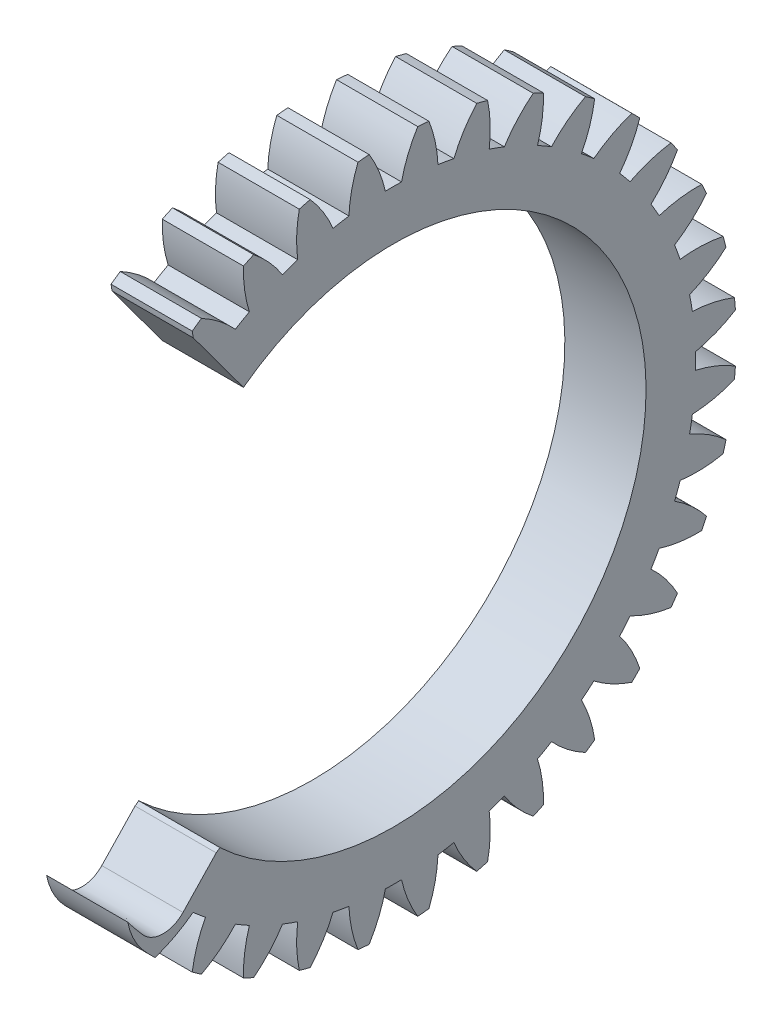
SolidWorks part; units mm, degrees
ref_plane "Plane1" through (0, 0, 0) normal (0, 0, 1) x (1, 0, 0)
ref_plane "Plane2" through (0, 0, 0) normal (0, 1, 0) x (1, 0, 0)
ref_plane "Plane3" through (0, 0, 0) normal (1, 0, 0) x (0, 0, -1)
sketch "HoldingSke" plane through (0, 0, 0) normal (0, 1, 0) x (1, 0, 0)
  line L0 (0, 0) -> (0.4045, -0.2939)
  line L1 (-15, 0) -> (100, 0) construction
  line L2 (0, 0) -> (-2.1039, 2.3779)
  line L3 (0, 0) -> (-11.863, 4.5341)
  line L4 (0, 0) -> (6.9867, 5.0761)
  line L5 (0, 0) -> (-46.8476, -17.4728)
  line L6 (0, 0) -> (-7.4607, -5.0337)
  line L7 (-2.1039, 2.3779) -> (8.6586, 51.2059)
  line L8 (-76.2, 54.61) -> (-71.9, 54.61)
  line L9 (-71.009, 38.7566) -> (-53.1078, 45.2721)
  line L10 (-76.2, 71.12) -> (104.1128, 71.12)
  line L11 (0, 0) -> (-9, 0)
  line L12 (-76.2, 101.6) -> (-76.133, 101.6)
  line L13 (24.9733, 27.94) -> (52.9518, 28.4284)
  line L14 (24.9733, 27.94) -> (24.9743, 27.94)
  line L15 (24.9733, 27.94) -> (100.4006, 29.5858)
  line L16 (-63.627, -2) -> (-12.827, -2)
  circle A0 centre (0, 0) radius 28
  circle A1 centre (0, 0) radius 33.499
  circle A2 centre (0, 0) radius 37.5
  circle A3 centre (0, 0) radius 28
  dimension "Num_teeth" = 36
  dimension "Pitch_radius" = 180.3128
  dimension "Width" = 9
  dimension "Thickness" = 9
sketch "BasProSke" plane through (0, 0, 0) normal (0, 1, 0) x (1, 0, 0)
  line L0 (-10, 0) -> (60, 0) construction
  line L1 (0, 0) -> (0, 38)
  line L2 (0, 0) -> (9, 0)
  line L3 (9, 0) -> (9, 38)
  line L4 (9, 38) -> (0, 38)
  dimension "Thickness" = 9
  dimension "Diameter" = 76
revolve "Base-Revolve" add sketch "BasProSke" angle 360 about L0
sketch "TooCutSke" plane through (0, 0, 0) normal (1, 0, 0) x (0, 0, -1)
  line L1 (0, 0) -> (0, 107) construction
  line L2 (0, 0) -> (-1.6875, 35.9604) construction
  line L3 (0, 0) -> (-6.2701, 71.6676) construction
  line L4 (-1.6875, 35.9604) -> (-3.135, 35.8338) construction
  arc A0 (0.8949, 33.487) -> (-0.8949, 33.487) centre (0, 0) ccw
  arc A1 (2.7061, 37.929) -> (-2.7061, 37.929) centre (0, 0) ccw
  circle A2 centre (0, 0) radius 36 construction
  circle A3 centre (0, 0) radius 33.8289 construction
  arc A4 (-0.8949, 33.487) -> (-2.7061, 37.929) centre (-14.9484, 30.347) ccw
  arc A5 (2.7061, 37.929) -> (0.8949, 33.487) centre (14.9484, 30.347) ccw
extrude "ToothCut" cut sketch "TooCutSke" along normal through all
fillet "Breaks" [suppressed] radius 0.04 tangent propagation no
fillet "RootFillets" [suppressed] radius 0.501
pattern_circular "TeethCuts" count 36 every 10 about axis through (-10, 0, 0) along (1, 0, 0) of "ToothCut", "RootFillets", "Breaks"
sketch "HubNeaOneSke" plane through (0, 0, 0) normal (-1, 0, 0) x (0, 0, 1)
  circle A0 centre (0, 0) radius 33.499
  dimension "Diameter" = 66.998
extrude "HubNearOne" [suppressed] add sketch "HubNeaOneSke" along normal blind 41.0001
sketch "HubNeaBotSke" plane through (0, 0, 0) normal (-1, 0, 0) x (0, 0, 1)
  circle A0 centre (0, 0) radius 33.499
  dimension "Diameter" = 66.998
extrude "HubNearBoth" [suppressed] add sketch "HubNeaBotSke" along normal blind 20.5
ref_plane "FarPln" through (9, 0, 0) normal (1, 0, 0) x (0, 0, -1)
sketch "HubFarSke" plane through (9, 0, 0) normal (1, 0, 0) x (0, 0, -1)
  circle A0 centre (0, 0) radius 33.499
  dimension "Diameter" = 66.998
extrude "HubFar" [suppressed] add sketch "HubFarSke" along normal blind 20.5
sketch "BorSke" plane through (0, 0, 0) normal (1, 0, 0) x (0, 0, -1)
  circle A0 centre (0, 0) radius 28
  dimension "Diameter" = 56
extrude "Bore" cut sketch "BorSke" along normal mid plane 100.0001
sketch "KeySke" plane through (0, 0, 0) normal (1, 0, 0) x (0, 0, -1)
  line L0 (-8, 0) -> (-8, 32.3)
  line L1 (-8, 32.3) -> (8, 32.3)
  line L2 (8, 32.3) -> (8, 0)
  line L3 (0, 0) -> (0, 34) construction
  line L4 (-8, 0) -> (8, 0)
  dimension "Width" = 16
extrude "Keyway" [suppressed] cut sketch "KeySke" along normal mid plane 100.0001
pattern_circular "Keyway2" [suppressed] count 2 every 90 about axis through (-10, 0, 0) along (1, 0, 0) reverse direction yes
sketch "Szkic1" plane through (0, 0, 0) normal (1, 0, 0) x (0, 0, -1)
  line L0 (0, 0) -> (-27.328, 37.0259)
  line L1 (-27.328, 37.0259) -> (-47.6164, -10.233)
  line L2 (-47.6164, -10.233) -> (0, 0)
extrude "Wytnij-wyciągnięcie1" cut sketch "Szkic1" along normal through all
sketch "Szkic2" plane through (0, 0, 0) normal (1, 0, 0) x (0, 0, -1)
  line L0 (-19.6433, -20.6493) -> (-23.3286, -24.5233) construction
  line L1 (-19.6433, -20.6493) -> (-23.3286, -24.5233)
  line L2 (-24.5118, 27.7159) -> (-14.2182, -16.6493)
  line L3 (-14.2182, -16.6493) -> (-19.6433, -20.6493)
  line L4 (-24.5118, 27.7159) -> (-50.9594, 25.255)
  line L5 (-50.9594, 25.255) -> (-37.7356, -29.3697)
  line L6 (-37.7356, -29.3697) -> (-27.7664, -24.4546)
  line L7 (-26.426, -27.3069) -> (-27.3069, -26.426)
  line L8 (-26.426, -27.3069) -> (-25.0675, -25.4318)
  arc A0 (-24.5118, 27.7159) -> (-27.7664, -24.4546) centre (0, 0) ccw construction
  arc A1 (-24.5118, 27.7159) -> (-27.7664, -24.4546) centre (0, 0) ccw
  arc A2 (-27.3069, -26.426) -> (-29.4473, -22.4022) centre (-21.7924, -20.9115) cw
  spline S0 degree 3 poles (101412.4792, 125980.3331) (3768.2153, 5027.8466) (-117.7155, 42.3759) (-27.1426, -24.9996) (-26.9606, -25.1074) (-26.5829, -25.2806) (-26.3868, -25.3469) (-25.9801, -25.4387) (-25.7711, -25.4633) (-25.3572, -25.469) (-25.1483, -25.4503) (-24.7384, -25.37) (-24.5404, -25.3094) (-24.158, -25.1482) (-23.9725, -25.0463) (75.8451, 43.9976) (-4185.8591, 5812.9515) (-98051.1547, 128688.4978) knots -67.877704 -67.877704 -67.877704 -67.877704 0.125 0.125 0.25 0.25 0.375 0.375 0.5 0.5 0.625 0.625 0.75 0.75 0.875 0.875 73.84833 73.84833 73.84833 73.84833 only from (-27.7664, -24.4546) to (-23.3286, -24.5233) construction
  spline S1 degree 3 poles (-27.7664, -24.4546) (-27.6277, -24.6121) (-27.4749, -24.7523) (-27.1426, -24.9996) (-26.9606, -25.1074) (-26.5829, -25.2806) (-26.3868, -25.3469) (-25.9801, -25.4387) (-25.7711, -25.4633) (-25.3572, -25.469) (-25.1483, -25.4503) (-24.7384, -25.37) (-24.5404, -25.3094) (-24.158, -25.1482) (-23.9725, -25.0463) (-23.6312, -24.8102) (-23.4733, -24.6754) (-23.3286, -24.5233) knots 0 0 0 0 0.125 0.125 0.25 0.25 0.375 0.375 0.5 0.5 0.625 0.625 0.75 0.75 0.875 0.875 1 1 1 1
extrude "Wytnij-wyciągnięcie2" cut sketch "Szkic2" against normal blind 43 and the other way through all contours A1 L4 L5 L6 | A1 S1 L1 L3 L2 region at (0, -1.5762, 26.5296) region at (0, 4.8425, 39.1923)
extrude "Dodanie-wyciągnięcie1" add sketch "Szkic2<3>" along normal up to surface (9 mm away) contours A2 L6 A1 | S1 L6 A2 L7 L8 region at (0, -25.7946, 26.8655) region at (0, -23.8723, 28.649) up to face at (9, -1.2954, -9.9994)
sketch "Szkic2<3>" plane through (0, 0, 0) normal (1, 0, 0) x (0, 0, -1) same geometry as "Szkic2"
equation "' \"Module@HoldingSke\" = 6.35"
equation "' \"Num_teeth@HoldingSke\" = 12"
equation "' \"Ap@HoldingSke\" =  20"
equation "' \"Ap@HoldingSke\" = 20"
equation "' \"Width@HoldingSke\" = 0.5 * 25.4"
equation "' \"Hub_dia@HoldingSke\"= 1 * 25.4"
equation "' \"Hub_dia@HoldingSke\" = 1 * 25.4"
equation "' \"Overall_len@HoldingSke\" = 1.0 * 25.4"
equation "' \"Bore@HoldingSke\" = 0.75 * 25.4"
equation "' \"T_dim@HoldingSke\" = 0.1 * 25.4"
equation "' \"Width@KeySke\" = 0.25 * 25.4"
equation "' \"Show_teeth@HoldingSke\" = 13"
equation "' \"Backlash@HoldingSke\" = 0.009 * 25.4"
equation "' \"Addendum_fac@HoldingSke\" = 1.0"
equation "' \"Dedendum_fac@HoldingSke\" = 1.25"
equation "' \"Dedendum_add@HoldingSke\" = 0.00005 * 25.4"
equation "' \"Clearance_fac@HoldingSke\" = 0.25"
equation "\"Pitch@HoldingSke\" = 1 / \"Module@HoldingSke\""
equation "\"Overcut_dia@TooCutSke\" = (\"Num_teeth@HoldingSke\" + 2 * \"Addendum_fac@HoldingSke\") / \"Pitch@HoldingSke\" + 0.002 * 25.4"
equation "\"Pitch_dia@TooCutSke\" = \"Num_teeth@HoldingSke\" / \"Pitch@HoldingSke\""
equation "\"Base_dia@TooCutSke\" = \"Num_teeth@HoldingSke\" / \"Pitch@HoldingSke\" * cos((\"Ap@HoldingSke\"  * 3.14159265 / 180))"
equation "\"Root_dia@TooCutSke\" = (\"Num_teeth@HoldingSke\" + 2) / \"Pitch@HoldingSke\" - 2 * (\"Addendum_fac@HoldingSke\" + \"Dedendum_fac@HoldingSke\") / \"Pitch@HoldingSke\" - \"Dedendum_add@HoldingSke\" * 2"
equation "\"Half_ang@TooCutSke\" = 180 / \"Num_teeth@HoldingSke\""
equation "\"Half_CT@TooCutSke\" = \"Num_teeth@HoldingSke\" / \"Pitch@HoldingSke\" * sin((3.14159265 / 2 / \"Num_teeth@HoldingSke\")) / 2 - 7 * \"Backlash@HoldingSke\" / 4"
equation "\"Flank_rad@TooCutSke\" = \"Num_teeth@HoldingSke\" / \"Pitch@HoldingSke\" / 5"
equation "\"Radius@RootFillets\" = \"Clearance_fac@HoldingSke\" / \"Pitch@HoldingSke\" + \"Dedendum_add@HoldingSke\""
equation "\"Break_rad@Breaks\" = 0.02 / \"Pitch@HoldingSke\""
equation "\"Thickness@HoldingSke\" = \"Width@HoldingSke\""
equation "\"OAL@HoldingSke\" = \"Thickness@HoldingSke\""
equation "\"MHD@HoldingSke\" = (\"Num_teeth@HoldingSke\" + 2) / \"Pitch@HoldingSke\" - 2 * (\"Addendum_fac@HoldingSke\" + \"Dedendum_fac@HoldingSke\")  / \"Pitch@HoldingSke\" - \"Dedendum_add@HoldingSke\" * 2"
equation "\"MBD@HoldingSke\" = (\"Num_teeth@HoldingSke\" + 2) / \"Pitch@HoldingSke\" - 2 * (\"Addendum_fac@HoldingSke\" + \"Dedendum_fac@HoldingSke\")  / \"Pitch@HoldingSke\" - \"Dedendum_add@HoldingSke\" * 2 - 0.002 * 25.4"
equation "\"MHD@HoldingSke\" = ((sgn( \"MHD@HoldingSke\" - \"Hub_dia@HoldingSke\" )-1)*( \"MHD@HoldingSke\" - \"Hub_dia@HoldingSke\" ))/-2+ \"Hub_dia@HoldingSke\""
equation "\"MBD@HoldingSke\" = ((sgn( \"MBD@HoldingSke\" - \"Bore@HoldingSke\" )-1)*( \"MBD@HoldingSke\" - \"Bore@HoldingSke\" ))/-2+ \"Bore@HoldingSke\""
equation "\"OAL@HoldingSke\" = ((sgn( \"OAL@HoldingSke\" - \"Overall_len@HoldingSke\" )+1)*( \"OAL@HoldingSke\" - \"Overall_len@HoldingSke\" ))/2 + \"Overall_len@HoldingSke\" + 0.000002 * 25.4"
equation "\"Num_teeth@TeethCuts\" = int( \"Show_teeth@HoldingSke\" ) + 1"
equation "\"Num_teeth@TeethCuts\" = ((sgn( \"Num_teeth@TeethCuts\" - \"Num_teeth@HoldingSke\" )-1)*( \"Num_teeth@TeethCuts\" - \"Num_teeth@HoldingSke\" ))/-2+ \"Num_teeth@HoldingSke\""
equation "\"Num_teeth@TeethCuts\" = ((sgn( \"Num_teeth@TeethCuts\" - 2.0)+1)*( \"Num_teeth@TeethCuts\" - 2.0))/2 +2.0"
equation "\"Angle@TeethCuts\" = 360.0 / \"Num_teeth@HoldingSke\""
equation "\"Diameter@BasProSke\" = (\"Num_teeth@HoldingSke\" + 2 * \"Addendum_fac@HoldingSke\") / \"Pitch@HoldingSke\""
equation "\"Thickness@BasProSke\"  = \"Thickness@HoldingSke\""
equation "' \"Fillet_rad@BasProSke\" =  \"Thickness@HoldingSke\" * 0.05"
equation "' \"Fillet_rad@BasProSke\" = \"Thickness@HoldingSke\" * 0.05"
equation "\"MHD@HoldingSke\" = ((sgn( \"MHD@HoldingSke\" - \"Root_dia@TooCutSke\" )-1)*( \"MHD@HoldingSke\" - \"Root_dia@TooCutSke\" ))/-2+ \"Root_dia@TooCutSke\""
equation "\"Diameter@HubNeaOneSke\" = \"MHD@HoldingSke\""
equation "\"Length@HubNearOne\" = \"OAL@HoldingSke\" - \"Thickness@BasProSke\""
equation "\"Diameter@HubNeaBotSke\" = \"MHD@HoldingSke\""
equation "\"Length@HubNearBoth\" = ( \"OAL@HoldingSke\" - \"Thickness@BasProSke\" ) / 2.0"
equation "\"Thickness@FarPln\" = \"Thickness@BasProSke\""
equation "\"Diameter@HubFarSke\" = \"MHD@HoldingSke\""
equation "\"Length@HubFar\" = ( \"OAL@HoldingSke\" - \"Thickness@BasProSke\" ) / 2.0"
equation "\"Diameter@BorSke\" = \"MBD@HoldingSke\""
equation "\"D1@Bore\" = \"OAL@HoldingSke\" * 2.0"
equation "\"D1@Keyway\" = \"OAL@HoldingSke\" * 2.0"
equation "\"Offset@KeySke\" = \"T_dim@HoldingSke\" + \"MBD@HoldingSke\" / 2.0"
